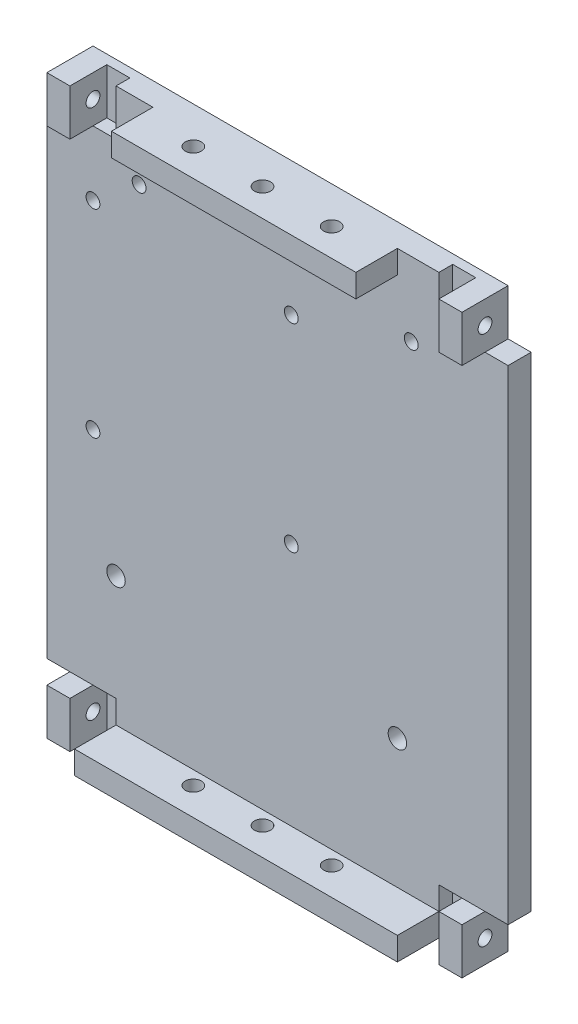
SolidWorks part; units mm, degrees
ref_plane "Front Plane" through (0, 0, 0) normal (0, 0, 1) x (1, 0, 0)
ref_plane "Top Plane" through (0, 0, 0) normal (0, 1, 0) x (1, 0, 0)
ref_plane "Right Plane" through (0, 0, 0) normal (1, 0, 0) x (0, 0, -1)
sketch "Sketch1" plane through (0, 0, 0) normal (0, 0, 1) x (1, 0, 0)
  line L1 (-95, 125) -> (-5, 125)
  line L2 (-95, 125) -> (-95, 0)
  line L3 (-95, 0) -> (-5, 0)
  line L4 (-5, 125) -> (-5, 0)
extrude "Boss-Extrude1" add sketch "Sketch1" along normal blind 5
sketch "Sketch2" plane through (-95, 0, 0) normal (-1, 0, 0) x (0, 0, 1)
  line L0 (10, 115) -> (0, 115) construction
  line L1 (5, 115) -> (0, 115)
  line L2 (5, 115) -> (5, 10)
  line L3 (5, 10) -> (0, 10)
  line L4 (0, 115) -> (0, 10)
  line L5 (0, 125) -> (0, 0) construction
  line L6 (10, 10) -> (0, 10) construction
extrude "Boss-Extrude2" add sketch "Sketch2" along normal up to surface (5 mm away)
sketch "Sketch3" plane through (0, 0, 5) normal (0, 0, 1) x (1, 0, 0)
  line L1 (-5, 125) -> (-10, 125)
  line L2 (-5, 125) -> (-5, 115)
  line L3 (-5, 115) -> (-10, 115)
  line L4 (-10, 125) -> (-10, 115)
  line L5 (-95, 125) -> (-90, 125)
  line L6 (-95, 125) -> (-95, 115)
  line L7 (-95, 115) -> (-90, 115)
  line L8 (-90, 125) -> (-90, 115)
  line L9 (-5, 0) -> (-10, 0)
  line L10 (-5, 0) -> (-5, 10)
  line L11 (-5, 10) -> (-10, 10)
  line L12 (-10, 0) -> (-10, 10)
  line L13 (-95, 0) -> (-90, 0)
  line L14 (-95, 0) -> (-95, 10)
  line L15 (-95, 10) -> (-90, 10)
  line L16 (-90, 0) -> (-90, 10)
  dimension "D1" = 5
  dimension "D2" = 10
extrude "Boss-Extrude3" add sketch "Sketch3" along normal up to surface (5 mm away)
sketch "Sketch4" plane through (0, 0, 5) normal (0, 0, 1) x (1, 0, 0)
  line L0 (-90, 0) -> (-10, 0) construction
  line L1 (-90, 125) -> (-85, 125)
  line L2 (-90, 125) -> (-90, 115)
  line L3 (-90, 115) -> (-85, 115)
  line L4 (-85, 125) -> (-85, 115)
  line L5 (-10, 125) -> (-15, 125)
  line L6 (-10, 125) -> (-10, 115)
  line L7 (-10, 115) -> (-15, 115)
  line L8 (-15, 125) -> (-15, 115)
  line L9 (-10, 0) -> (-15, 0)
  line L10 (-10, 0) -> (-10, 10)
  line L11 (-10, 10) -> (-15, 10)
  line L12 (-15, 0) -> (-15, 10)
  line L13 (-90, 0) -> (-85, 0)
  line L14 (-90, 0) -> (-90, 10)
  line L15 (-90, 10) -> (-85, 10)
  line L16 (-85, 0) -> (-85, 10)
  dimension "D1" = 5
  dimension "D2" = 10
extrude "Cut-Extrude1" cut sketch "Sketch4" against normal blind 3
sketch "Sketch5" plane through (0, 0, 0) normal (1, 0, 0) x (0, 0, -1)
  circle A0 centre (-5, 5) radius 1.5
  circle A1 centre (-5, 120) radius 1.5
extrude "Cut-Extrude2" cut sketch "Sketch5" against normal up to surface (15 mm away) up to face at (-15, 5, 3.5)
sketch "Sketch6" plane through (-100, 0, 0) normal (-1, 0, 0) x (0, 0, 1)
  circle A0 centre (5, 5) radius 1.5
  circle A1 centre (5, 120) radius 1.5
extrude "Cut-Extrude3" cut sketch "Sketch6" against normal up to surface (15 mm away) up to face at (-85, 120, 3.5)
sketch "Sketch7" plane through (0, 0, 5) normal (0, 0, 1) x (1, 0, 0)
  line L0 (-15, 125) -> (-85, 125) construction
  line L1 (-77, 125) -> (-24, 125)
  line L2 (-77, 125) -> (-77, 120)
  line L3 (-77, 120) -> (-24, 120)
  line L4 (-24, 125) -> (-24, 120)
  line L5 (-85, 0) -> (-85, 10) construction
  line L6 (-85, 0) -> (-15, 0)
  line L7 (-85, 0) -> (-85, 5)
  line L8 (-85, 5) -> (-15, 5)
  line L9 (-15, 0) -> (-15, 5)
  line L10 (-15, 10) -> (-15, 0) construction
  line L11 (-85, 0) -> (-15, 0) construction
  dimension "D1" = 0
  dimension "D2" = 5
  dimension "D3" = 5
extrude "Boss-Extrude4" add sketch "Sketch7" along normal up to surface (9 mm away)
sketch "Sketch8" plane through (0, 0, 0) normal (0, -1, 0) x (1, 0, 0)
  circle A0 centre (-65.25, 8) radius 1.75
  circle A1 centre (-50.25, 8) radius 1.75
  circle A2 centre (-35.25, 8) radius 1.75
extrude "Cut-Extrude4" cut sketch "Sketch8" against normal up to surface (125 mm away) up to face at (-49.5937, 125, 6.25)
sketch "Sketch9" plane through (0, 0, 5) normal (0, 0, 1) x (1, 0, 0)
  line L0 (-100, 115) -> (-100, 10) construction
  line L1 (-77, 125) -> (-85, 125) construction
  circle A0 centre (-47, 101) radius 1.5
  circle A1 centre (-90, 101) radius 1.5
  circle A2 centre (-90, 58) radius 1.5
  circle A3 centre (-47, 58) radius 1.5
  dimension "D1" = 3
  dimension "D4" = 10
  dimension "D5" = 24
  dimension "D2" = 43
  dimension "D3" = 43
extrude "Cut-Extrude5" cut sketch "Sketch9" against normal up to surface (5 mm away) up to face at (-74.375, 63.75, 0)
sketch "Sketch10" plane through (0, 0, 5) normal (0, 0, 1) x (1, 0, 0)
  line L2 (-100, 115) -> (-100, 10) construction
  circle A0 centre (-85, 33) radius 2
  circle A1 centre (-24, 33) radius 2
  circle A2 centre (-90, 58) radius 1.5 construction
  dimension "D1" = 4
  dimension "D2" = 25
  dimension "D4" = 15
  dimension "D3" = 61
extrude "Cut-Extrude6" cut sketch "Sketch10" against normal up to surface (5 mm away) up to face at (-45.5, 58, 0)
sketch "Sketch11" plane through (-5, 0, 0) normal (1, 0, 0) x (0, 0, -1)
  line L0 (0, 0) -> (0, 125) construction
  line L1 (-5, 115) -> (0, 115)
  line L2 (-5, 115) -> (-5, 10)
  line L3 (-5, 10) -> (0, 10)
  line L4 (0, 115) -> (0, 10)
extrude "Boss-Extrude5" add sketch "Sketch11" along normal blind 5
sketch "Sketch12" plane through (0, 0, 0) normal (0, 0, -1) x (-1, 0, 0)
  line L0 (5, 125) -> (95, 125) construction
  line L1 (77, 103) -> (83.5, 103)
  line L2 (77, 103) -> (77, 120)
  line L3 (77, 120) -> (83.5, 120)
  line L4 (83.5, 103) -> (83.5, 120)
  line L5 (24, 103) -> (17.5, 103)
  line L6 (24, 103) -> (24, 120)
  line L7 (24, 120) -> (17.5, 120)
  line L8 (17.5, 103) -> (17.5, 120)
  line L11 (85, 115) -> (85, 125) construction
  dimension "D1" = 17
  dimension "D2" = 6.5
  dimension "D3" = 17
  dimension "D4" = 6.5
  dimension "D5" = 5
  dimension "D6" = 53
  dimension "D7" = 8
extrude "Cut-Extrude7" cut sketch "Sketch12" against normal blind 2
sketch "Sketch13" plane through (0, 0, 2) normal (0, 0, -1) x (-1, 0, 0)
  line L0 (17.5, 103) -> (24, 103) construction
  line L1 (24, 103) -> (24, 120) construction
  line L2 (77, 120) -> (77, 103) construction
  circle A0 centre (80, 109) radius 1.5
  circle A1 centre (21, 109) radius 1.5
  dimension "D2" = 3
  dimension "D3" = 3
  dimension "D4" = 3
  dimension "D1" = 6
extrude "Cut-Extrude8" cut sketch "Sketch13" against normal up to surface (3 mm away) up to face at (-22, 33, 5)
